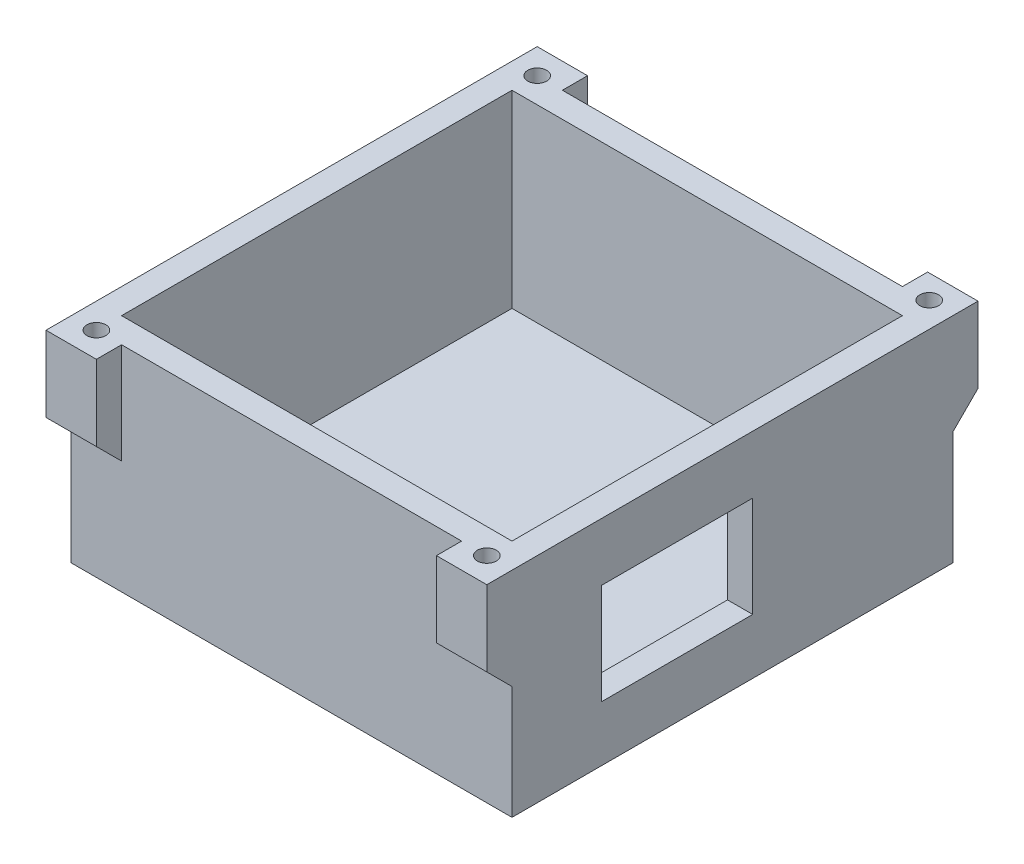
SolidWorks part; units mm, degrees
ref_plane "Front Plane" through (0, 0, 0) normal (0, 0, 1) x (1, 0, 0)
ref_plane "Top Plane" through (0, 0, 0) normal (0, 1, 0) x (1, 0, 0)
ref_plane "Right Plane" through (0, 0, 0) normal (1, 0, 0) x (0, 0, -1)
sketch "Sketch1" plane through (0, 0, 0) normal (0, 1, 0) x (1, 0, 0)
  line L0 (-2, -2) -> (-2, 33)
  line L1 (0, 0) -> (31, 0)
  line L2 (0, 0) -> (0, 31)
  line L3 (0, 31) -> (31, 31)
  line L4 (31, 0) -> (31, 31)
  line L5 (-2, 33) -> (33, 33)
  line L6 (33, -2) -> (33, 33)
  line L7 (-2, -2) -> (33, -2)
  dimension "D1" = 31
  dimension "D2" = 31
  dimension "D3" = 2
extrude "Boss-Extrude1" add sketch "Sketch1" along normal blind 2 contours L1 L4 L3 L2 | L0 L7 L6 L5 L4 L1 L2 L3 region at (-1.505, 0, -15.5) region at (15.5, 0, -15.5)
extrude "Boss-Extrude2" add sketch "Sketch1<3>" along normal offset from surface (17 mm away) 15 up to face at (15.5, 2, -15.5) offset beyond the face yes
sketch "Sketch1<3>" plane through (0, 0, 0) normal (0, 1, 0) x (1, 0, 0) same geometry as "Sketch1"
sketch "Sketch2" plane through (33, 0, 0) normal (1, 0, 0) x (0, 0, -1)
  line L0 (31, 2) -> (0, 2) construction
  line L1 (5.1113, 12.4) -> (17.1113, 12.4)
  line L2 (5.1113, 12.4) -> (5.1113, 4.4)
  line L3 (5.1113, 4.4) -> (17.1113, 4.4)
  line L4 (17.1113, 12.4) -> (17.1113, 4.4)
  dimension "D1" = 12
  dimension "D2" = 8
  dimension "D3" = 2.4
extrude "Cut-Extrude1" cut sketch "Sketch2" against normal blind 15
sketch "Sketch3" plane through (0, 17, 0) normal (0, 1, 0) x (1, 0, 0)
  line L1 (33, -2) -> (29, -2)
  line L2 (33, -2) -> (33, -4)
  line L3 (33, -4) -> (29, -4)
  line L4 (29, -2) -> (29, -4)
  line L5 (-2, -2) -> (2, -2)
  line L6 (-2, -2) -> (-2, -4)
  line L7 (-2, -4) -> (2, -4)
  line L8 (2, -2) -> (2, -4)
  line L9 (-2, 33) -> (2, 33)
  line L10 (-2, 33) -> (-2, 35)
  line L11 (-2, 35) -> (2, 35)
  line L12 (2, 33) -> (2, 35)
  line L13 (33, 33) -> (29, 33)
  line L14 (33, 33) -> (33, 35)
  line L15 (33, 35) -> (29, 35)
  line L16 (29, 33) -> (29, 35)
  line M14 (-2, -2) -> (33, -2)
  line M16 (33, 33) -> (-2, 33)
  dimension "D1" = 4
  dimension "D2" = 2
  dimension "D3" = 2
  dimension "D4" = 4
  dimension "D5" = 4
  dimension "D6" = 2
  dimension "D7" = 4
  dimension "D8" = 2
extrude "Boss-Extrude3" add sketch "Sketch3" against normal blind 6 contours L16 L14 L15 M16 | L12 L11 L10 M16 | L8 L6 L7 M14 | L4 L3 L2 M14 region at (31, 17, 3) region at (0, 17, 3) region at (0, 17, -34) region at (31, 17, -34)
chamfer "Chamfer1" distance 2 angle 45 4 edges at (31, 11, 2) (0, 11, 2) (0, 11, -33) (31, 11, -33)
sketch "Sketch4" plane through (0, 17, 0) normal (0, 1, 0) x (1, 0, 0)
  line L1 (31, 31) -> (31, 0) construction
  line L2 (31, 0) -> (31, 31) construction
  line L3 (2, -2) -> (29, -2) construction
  line L4 (0, 0) -> (0, 31) construction
  line L5 (0, 31) -> (0, 0) construction
  line L6 (29, 33) -> (2, 33) construction
  circle A0 centre (31, 33.1225) radius 0.75
  circle A1 centre (31, -2) radius 0.75
  circle A2 centre (0, -2) radius 0.75
  circle A3 centre (0, 33) radius 0.75
  point P8 (0, 0)
  point P11 (0, 0)
  point P14 (0, 0)
  point P17 (0, 0)
  point P18 (0, 0)
  point P21 (0, -2)
  point P24 (0, 0)
  dimension "D1" = 1.5
  dimension "D2" = 1.5
  dimension "D3" = 1.5
  dimension "D4" = 1.5
extrude "Cut-Extrude2" cut sketch "Sketch4" against normal blind 6
